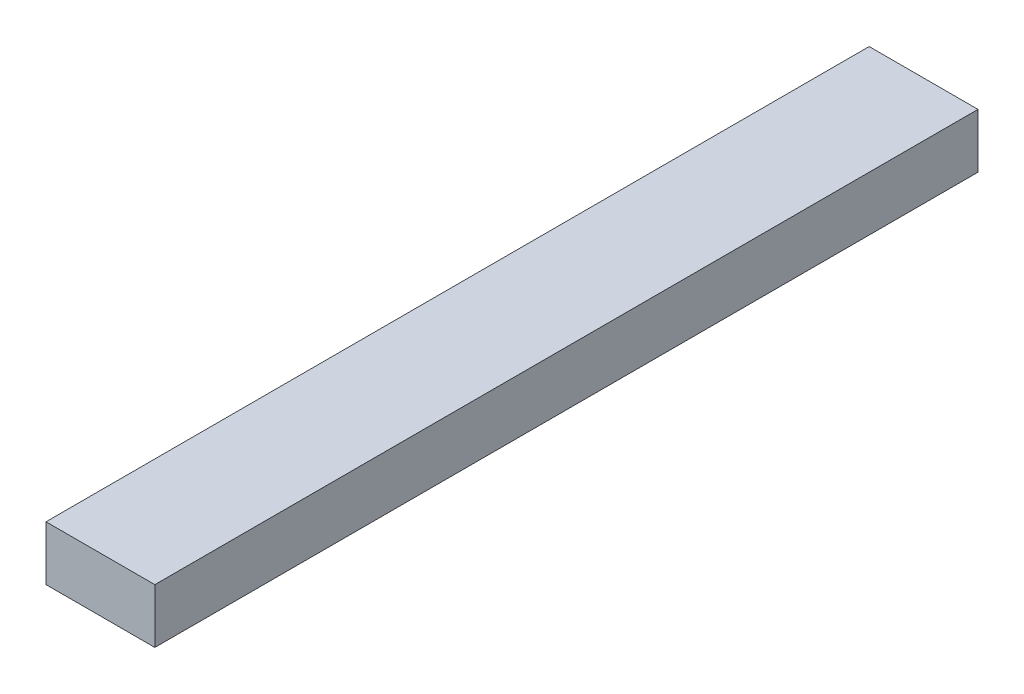
SolidWorks part; units mm, degrees
ref_plane "Front Plane" through (0, 0, 0) normal (0, 0, 1) x (1, 0, 0)
ref_plane "Top Plane" through (0, 0, 0) normal (0, 1, 0) x (1, 0, 0)
ref_plane "Right Plane" through (0, 0, 0) normal (1, 0, 0) x (0, 0, -1)
sketch "Sketch1" plane through (0, 0, 0) normal (0, 0, 1) x (1, 0, 0)
  line L1 (0, 0) -> (50.8, 0)
  line L2 (0, 0) -> (0, 25.4)
  line L3 (0, 25.4) -> (50.8, 25.4)
  line L4 (50.8, 0) -> (50.8, 25.4)
  dimension "D1" = 25.4
  dimension "D2" = 50.8
extrude "Boss-Extrude1" add sketch "Sketch1" along normal blind 384.175
